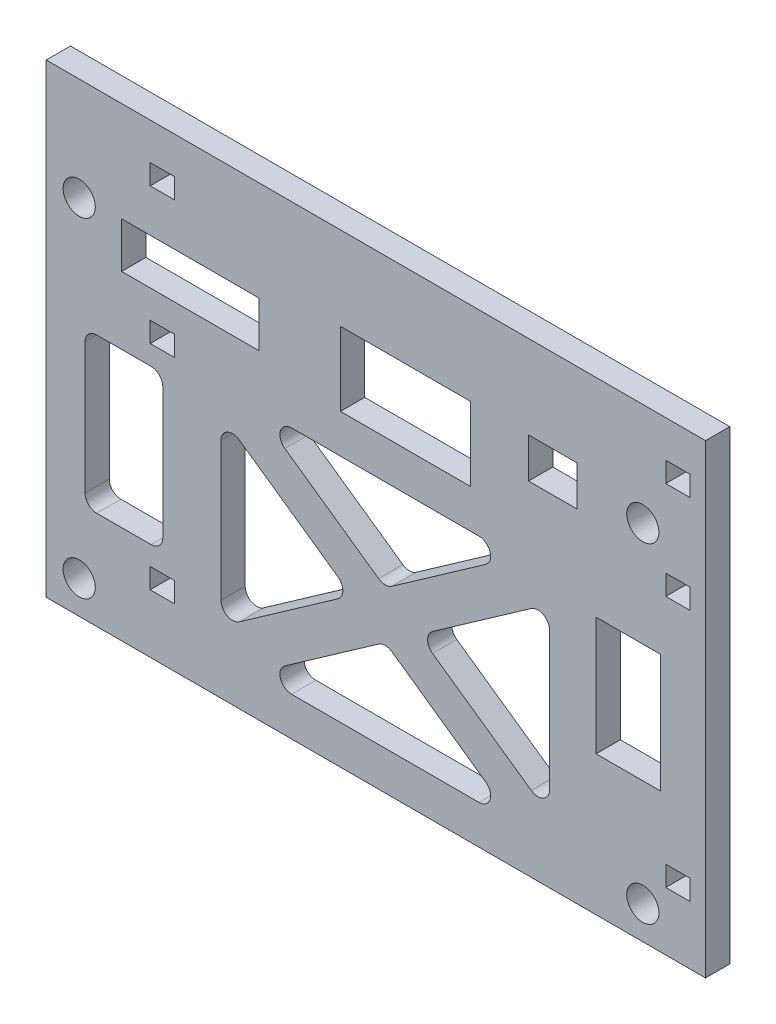
SolidWorks part; units mm, degrees
material "Beech"
ref_plane "Front Plane" through (0, 0, 0) normal (0, 0, 1) x (1, 0, 0)
ref_plane "Top Plane" through (0, 0, 0) normal (0, 1, 0) x (1, 0, 0)
ref_plane "Right Plane" through (0, 0, 0) normal (1, 0, 0) x (0, 0, -1)
sketch "Sketch1" plane through (0, 0, 0) normal (0, 0, 1) x (1, 0, 0)
  line L0 (-21.59, 0) -> (21.59, 0)
  line L44 (0, 14.605) -> (0, 24.13) construction
  line L46 (-21.59, 0) -> (-21.59, 30.48)
  line L47 (-21.59, 30.48) -> (21.59, 30.48)
  line L48 (21.59, 0) -> (21.59, 30.48)
  line L49 (-21.59, 12.7) -> (21.59, 12.7) construction
  circle A0 centre (17.4828, 2.159) radius 1.0541
  circle A1 centre (17.4828, 23.749) radius 1.0541
  circle A2 centre (-19.431, 2.159) radius 1.0541
  circle A3 centre (-19.431, 23.749) radius 1.0541
  point P0 (0, 0)
  point P56 (0, 12.7)
  point P60 (0, 30.48)
  dimension "D14" = 17.78
  dimension "D4" = 2.1082
  dimension "D2" = 12.7
  dimension "D3" = 2.159
  dimension "D12" = 43.18
  dimension "D5" = 2.159
  dimension "D6" = 2
  dimension "D7" = 2
extrude "Boss-Extrude1" add sketch "Sketch1" along normal blind 1.5875 contours L48 L47 L46 region at (0.0104, 15.2645, 0)
fillet "Fillet7" [suppressed] radius 15.24
sketch "Sketch5" plane through (0, 0, 1.5875) normal (0, 0, 1) x (1, 0, 0)
  line L0 (-16.651, 23.9432) -> (-16.651, 20.9573) construction
  line L1 (-16.651, 20.9573) -> (-7.651, 20.9573) construction
  line L2 (-7.651, 20.9573) -> (-7.651, 23.9432) construction
  line L3 (-7.651, 23.9432) -> (-16.651, 23.9432) construction
  line L12 (6.1886, 20.184) -> (6.1886, 25.01) construction
  line L13 (6.1886, 25.01) -> (-2.3204, 25.01) construction
  line L14 (-2.3204, 25.01) -> (-2.3204, 20.184) construction
  line L15 (-2.3204, 20.184) -> (6.1886, 20.184) construction
  line L16 (13.1736, 22.3938) -> (13.1736, 25.01) construction
  line L17 (13.1736, 25.01) -> (9.9986, 25.01) construction
  line L18 (9.9986, 25.01) -> (9.9986, 22.3938) construction
  line L19 (9.9986, 22.3938) -> (13.1736, 22.3938) construction
  line L20 (14.4226, 16.8835) -> (14.4226, 9.1335) construction
  line L21 (14.4226, 9.1335) -> (18.6426, 9.1335) construction
  line L22 (18.6426, 9.1335) -> (18.6426, 16.8835) construction
  line L23 (18.6426, 16.8835) -> (14.4226, 16.8835) construction
  line L24 (-16.651, 23.9432) -> (-16.651, 20.9573)
  line L25 (-16.651, 20.9573) -> (-7.651, 20.9573)
  line L26 (-7.651, 20.9573) -> (-7.651, 23.9432)
  line L27 (-7.651, 23.9432) -> (-16.651, 23.9432)
  line L28 (6.1886, 20.184) -> (6.1886, 25.01)
  line L29 (6.1886, 25.01) -> (-2.3204, 25.01)
  line L30 (-2.3204, 25.01) -> (-2.3204, 20.184)
  line L31 (-2.3204, 20.184) -> (6.1886, 20.184)
  line L32 (13.1736, 22.3938) -> (13.1736, 25.01)
  line L33 (13.1736, 25.01) -> (9.9986, 25.01)
  line L34 (9.9986, 25.01) -> (9.9986, 22.3938)
  line L35 (9.9986, 22.3938) -> (13.1736, 22.3938)
  line L36 (14.4226, 16.8835) -> (14.4226, 9.1335)
  line L37 (14.4226, 9.1335) -> (18.6426, 9.1335)
  line L38 (18.6426, 9.1335) -> (18.6426, 16.8835)
  line L39 (18.6426, 16.8835) -> (14.4226, 16.8835)
extrude "Camera Cuts" cut sketch "Sketch5" against normal up to next
sketch "Sketch6" plane through (0, 0, 1.5875) normal (0, 0, 1) x (1, 0, 0)
  line L0 (11.3746, 4.0915) -> (-7.9365, 17.644)
  line L1 (11.3746, 2.54) -> (-10.1473, 2.54)
  line L2 (11.3746, 2.54) -> (11.3746, 17.644)
  line L3 (11.3746, 17.644) -> (-10.1473, 17.644)
  line L4 (-10.1473, 2.54) -> (-10.1473, 17.644)
  line L5 (11.3746, 2.54) -> (-10.1473, 17.644) construction
  line L6 (11.3746, 17.644) -> (-10.1473, 2.54) construction
  line L7 (9.1638, 2.54) -> (-10.1473, 16.0925)
  line L8 (9.1638, 17.644) -> (-10.1473, 4.0915)
  line L9 (11.3746, 16.0925) -> (-7.9365, 2.54)
  line L10 (10.645, 1.5005) -> (-10.8769, 16.6045) construction
  line L11 (12.1042, 16.6045) -> (-9.4177, 1.5005) construction
  line L12 (10.645, 18.6835) -> (-10.8769, 3.5795) construction
  line L13 (12.1042, 3.5795) -> (-9.4177, 18.6835) construction
  line L14 (-21.59, 0) -> (21.59, 0) construction
  line L15 (14.4226, 16.8835) -> (14.4226, 9.1335) construction
  line L16 (-2.3204, 20.184) -> (6.1886, 20.184) construction
  line L18 (-21.59, 0) -> (-21.59, 30.48) construction
  line L19 (-19.05, 6.4248) -> (-13.9573, 6.4248)
  line L20 (-19.05, 6.4248) -> (-19.05, 16.534)
  line L21 (-19.05, 16.534) -> (-13.9573, 16.534)
  line L22 (-13.9573, 6.4248) -> (-13.9573, 16.534)
  line L23 (-19.05, 6.4248) -> (-13.9573, 16.534) construction
  line L24 (-19.05, 16.534) -> (-13.9573, 6.4248) construction
  line L27 (-13.1953, 5.1548) -> (-13.1953, 3.834) construction
  line L28 (-14.7828, 17.804) -> (-13.1953, 17.804) construction
  line L29 (-14.7828, 5.1548) -> (-13.1953, 5.1548) construction
  point P0 (0.6137, 10.092)
  point P29 (-16.5036, 11.4794)
  dimension "D5" = 2.54
  dimension "D6" = 3.048
  dimension "D7" = 2.54
  dimension "D8" = 3.048
  dimension "D9" = 2.54
  dimension "D10" = 1.27
  dimension "D11" = 1.27
  dimension "D12" = 3.81
  dimension "D1" = 1.27
  dimension "D2" = 1.27
  dimension "D3" = 1.27
  dimension "D4" = 1.27
extrude "Weight Reduction Cuts" cut sketch "Sketch6" against normal blind 2.54 contours L7 L9 L1 | L2 L9 L0 | L8 L3 L0 | L8 L7 L4 | L19 L22 L21 L20 region at (8.5246, 10.092, 1.5875) region at (0.6137, 15.6438, 1.5875) region at (0.6137, 4.5402, 1.5875) region at (-7.2973, 10.092, 1.5875) region at (-16.5036, 11.4794, 1.5875)
sketch "Sketch7" plane through (0, 0, 0) normal (0, 0, -1) x (-1, 0, 0)
  line L0 (13.1953, 28.0656) -> (13.1953, 26.7448) construction
  line L1 (13.1953, 26.7448) -> (14.7828, 26.7448) construction
  line L2 (14.7828, 26.7448) -> (14.7828, 28.0656) construction
  line L3 (14.7828, 28.0656) -> (13.1953, 28.0656) construction
  line L4 (13.1953, 19.1248) -> (13.1953, 17.804) construction
  line L5 (13.1953, 17.804) -> (14.7828, 17.804) construction
  line L6 (14.7828, 17.804) -> (14.7828, 19.1248) construction
  line L7 (14.7828, 19.1248) -> (13.1953, 19.1248) construction
  line L8 (13.1953, 5.1548) -> (13.1953, 3.834) construction
  line L9 (13.1953, 3.834) -> (14.7828, 3.834) construction
  line L10 (14.7828, 3.834) -> (14.7828, 5.1548) construction
  line L11 (14.7828, 5.1548) -> (13.1953, 5.1548) construction
  line L12 (-20.574, 5.1548) -> (-20.574, 3.834) construction
  line L13 (-20.574, 3.834) -> (-18.9865, 3.834) construction
  line L14 (-18.9865, 3.834) -> (-18.9865, 5.1548) construction
  line L15 (-18.9865, 5.1548) -> (-20.574, 5.1548) construction
  line L16 (-20.574, 21.6648) -> (-20.574, 20.344) construction
  line L17 (-20.574, 20.344) -> (-18.9865, 20.344) construction
  line L18 (-18.9865, 20.344) -> (-18.9865, 21.6648) construction
  line L19 (-18.9865, 21.6648) -> (-20.574, 21.6648) construction
  line L20 (-20.574, 28.0656) -> (-20.574, 26.7448) construction
  line L21 (-20.574, 26.7448) -> (-18.9865, 26.7448) construction
  line L22 (-18.9865, 26.7448) -> (-18.9865, 28.0656) construction
  line L23 (-18.9865, 28.0656) -> (-20.574, 28.0656) construction
  line L24 (13.1953, 28.0656) -> (13.1953, 26.7448)
  line L25 (13.1953, 26.7448) -> (14.7828, 26.7448)
  line L26 (14.7828, 26.7448) -> (14.7828, 28.0656)
  line L27 (14.7828, 28.0656) -> (13.1953, 28.0656)
  line L28 (13.1953, 19.1248) -> (13.1953, 17.804)
  line L29 (13.1953, 17.804) -> (14.7828, 17.804)
  line L30 (14.7828, 17.804) -> (14.7828, 19.1248)
  line L31 (14.7828, 19.1248) -> (13.1953, 19.1248)
  line L32 (13.1953, 5.1548) -> (13.1953, 3.834)
  line L33 (13.1953, 3.834) -> (14.7828, 3.834)
  line L34 (14.7828, 3.834) -> (14.7828, 5.1548)
  line L35 (14.7828, 5.1548) -> (13.1953, 5.1548)
  line L36 (-20.574, 5.1548) -> (-20.574, 3.834)
  line L37 (-20.574, 3.834) -> (-18.9865, 3.834)
  line L38 (-18.9865, 3.834) -> (-18.9865, 5.1548)
  line L39 (-18.9865, 5.1548) -> (-20.574, 5.1548)
  line L40 (-20.574, 21.6648) -> (-20.574, 20.344)
  line L41 (-20.574, 20.344) -> (-18.9865, 20.344)
  line L42 (-18.9865, 20.344) -> (-18.9865, 21.6648)
  line L43 (-18.9865, 21.6648) -> (-20.574, 21.6648)
  line L44 (-20.574, 28.0656) -> (-20.574, 26.7448)
  line L45 (-20.574, 26.7448) -> (-18.9865, 26.7448)
  line L46 (-18.9865, 26.7448) -> (-18.9865, 28.0656)
  line L47 (-18.9865, 28.0656) -> (-20.574, 28.0656)
extrude "Attachment Cuts" cut sketch "Sketch7" against normal up to next
fillet "Fillet8" radius 0.762 16 edges at (-10.1473, 4.0915, 0.7937) (-7.9365, 2.54, 0.7937) (9.1638, 2.54, 0.7937) (11.3746, 4.0915, 0.7937) (0.6137, 11.6435, 0.7937) (-7.9365, 17.644, 0.7937) (2.8245, 10.092, 0.7937) (0.6137, 8.5405, 0.7937) (-10.1473, 16.0925, 0.7937) (9.1638, 17.644, 0.7937) (-1.5972, 10.092, 0.7937) (11.3746, 16.0925, 0.7937) (-19.05, 16.534, 0.7937) (-19.05, 6.4248, 0.7937) (-13.9573, 6.4248, 0.7937) (-13.9573, 16.534, 0.7937)
